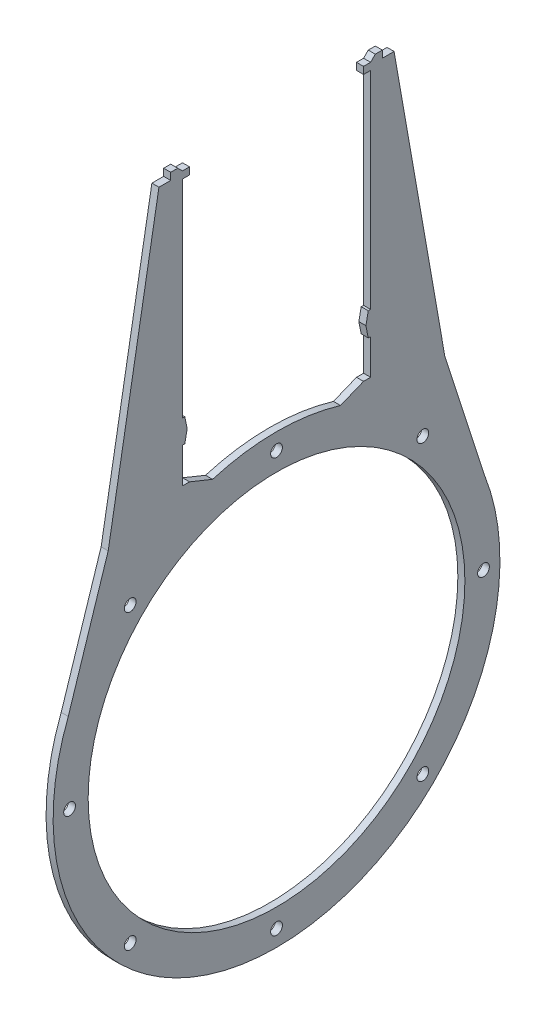
SolidWorks part; units mm, degrees
material "Stal węglowa"
ref_plane "Front" through (0, 0, 0) normal (0, 0, 1) x (1, 0, 0)
ref_plane "Top" through (0, 0, 0) normal (0, 1, 0) x (1, 0, 0)
ref_plane "Right" through (0, 0, 0) normal (1, 0, 0) x (0, 0, -1)
sketch "Szkic1" plane through (0, 0, 0) normal (1, 0, 0) x (0, 0, -1)
  line L138 (351.559, 167.8123) -> (351.559, 79.8123)
  line L139 (351.559, 69.8123) -> (351.559, 54.8123)
  line L140 (351.559, 54.8123) -> (348.559, 54.8123)
  line L141 (348.559, 54.8123) -> (338.7531, 50.837)
  line L142 (271.559, 69.8123) -> (271.559, 54.8123)
  line L143 (271.559, 79.8123) -> (271.559, 167.8123)
  line L144 (271.559, 54.8123) -> (274.559, 54.8123)
  line L145 (274.559, 54.8123) -> (284.3649, 50.837)
  line L146 (361.559, 169.8123) -> (383.1413, 46.6826)
  line L147 (383.1413, 46.6826) -> (400.1192, -5.8061)
  line L148 (269.559, 172.8123) -> (266.559, 172.8123)
  line L149 (266.559, 172.8123) -> (266.559, 169.8123)
  line L150 (266.559, 169.8123) -> (261.559, 169.8123)
  line L151 (261.559, 169.8123) -> (239.9766, 46.6826)
  line L152 (274.559, 170.8123) -> (274.559, 167.8123)
  line L153 (274.559, 167.8123) -> (271.559, 167.8123)
  line L154 (239.9766, 46.6826) -> (222.9988, -5.8061)
  line L155 (271.559, 79.8123) -> (272.559, 79.8123)
  line L156 (271.559, 69.8123) -> (272.559, 69.8123)
  line L157 (351.559, 69.8123) -> (350.559, 69.8123)
  line L158 (351.559, 79.8123) -> (350.559, 79.8123)
  line L159 (353.559, 172.8123) -> (351.559, 170.8123)
  line L160 (348.559, 170.8123) -> (351.559, 170.8123)
  line L161 (348.559, 167.8123) -> (351.559, 167.8123)
  line L162 (348.559, 170.8123) -> (348.559, 167.8123)
  line L163 (356.559, 172.8123) -> (356.559, 169.8123)
  line L164 (356.559, 169.8123) -> (361.559, 169.8123)
  line L165 (269.559, 172.8123) -> (271.559, 170.8123)
  line L166 (353.559, 172.8123) -> (356.559, 172.8123)
  line L167 (274.559, 170.8123) -> (271.559, 170.8123)
  line L168 (273.559, 74.8123) -> (272.559, 69.8123)
  line L169 (272.559, 79.8123) -> (273.559, 74.8123)
  line L170 (349.559, 74.8123) -> (350.559, 69.8123)
  line L171 (350.559, 79.8123) -> (349.559, 74.8123)
  circle A75 centre (311.559, -40.1877) radius 80.1
  circle A76 centre (311.559, 47.8123) radius 2.5
  circle A77 centre (249.3336, 22.0377) radius 2.5
  circle A78 centre (249.3336, -102.4131) radius 2.5
  circle A79 centre (311.559, -128.1877) radius 2.5
  circle A80 centre (373.7844, -102.4131) radius 2.5
  circle A81 centre (399.559, -40.1877) radius 2.5
  circle A82 centre (373.7844, 22.0377) radius 2.5
  arc A83 (338.7531, 50.837) -> (284.3649, 50.837) centre (311.559, -40.1877) ccw
  arc A84 (222.9988, -5.8061) -> (400.1192, -5.8061) centre (311.559, -40.1877) ccw
  circle A85 centre (223.559, -40.1877) radius 2.5
extrude "Dodanie-wyciągnięcie1" add sketch "Szkic1" along normal blind 3
